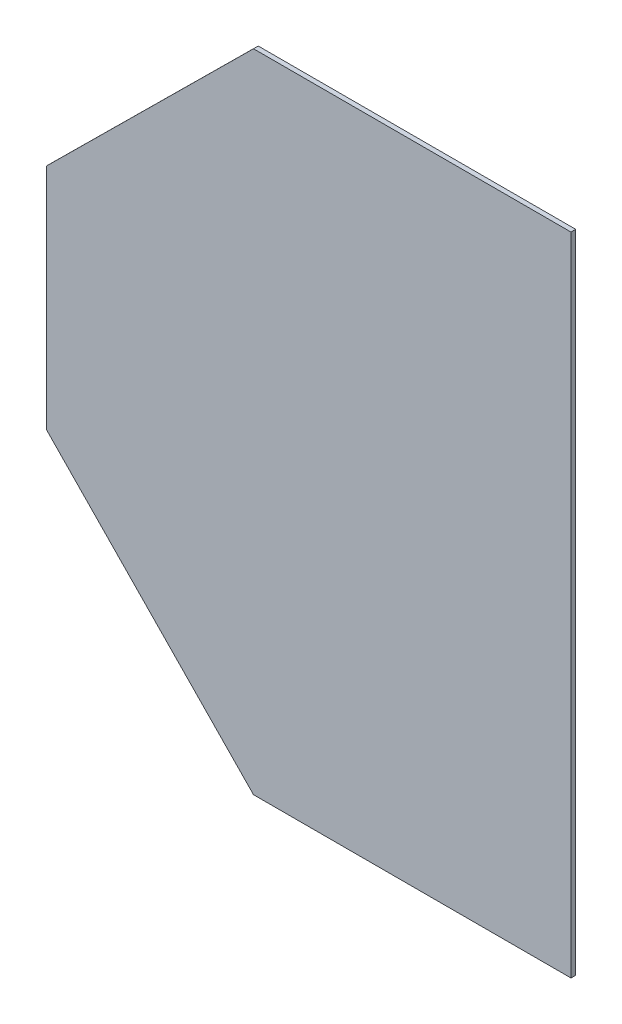
SolidWorks part; units mm, degrees
material "ASTM A500 Grade B"
ref_plane "Front Plane" through (0, 0, 0) normal (0, 0, 1) x (1, 0, 0)
ref_plane "Top Plane" through (0, 0, 0) normal (0, 1, 0) x (1, 0, 0)
ref_plane "Right Plane" through (0, 0, 0) normal (1, 0, 0) x (0, 0, -1)
sketch "Sketch1" plane through (0, 0, 0) normal (0, 0, 1) x (1, 0, 0)
  line L0 (-4.281, -146.7903) -> (-216.4881, -146.7903)
  line L1 (-4.281, -2487.2903) -> (-4.281, 2625.5097) construction
  line L2 (-216.4881, 285.0097) -> (-354.9957, 147.8379)
  line L4 (-354.9957, 147.8379) -> (-354.9957, -4.5621)
  line L6 (-354.9957, -4.5621) -> (-216.4881, -146.7903)
  line L7 (-216.4881, 285.0097) -> (-4.281, 285.0097)
  line L8 (-4.281, 285.0097) -> (-4.281, -146.7903)
  line L9 (-60.0478, 69.1097) -> (35.4026, 69.1097) construction
  line L10 (-60.0478, 119.9097) -> (-60.0478, 18.3097) construction
  dimension "D1" = 215.9
  dimension "D2" = 215.9
  dimension "D3" = 152.4
extrude "Boss-Extrude1" add sketch "Sketch1" along normal blind 3.175
